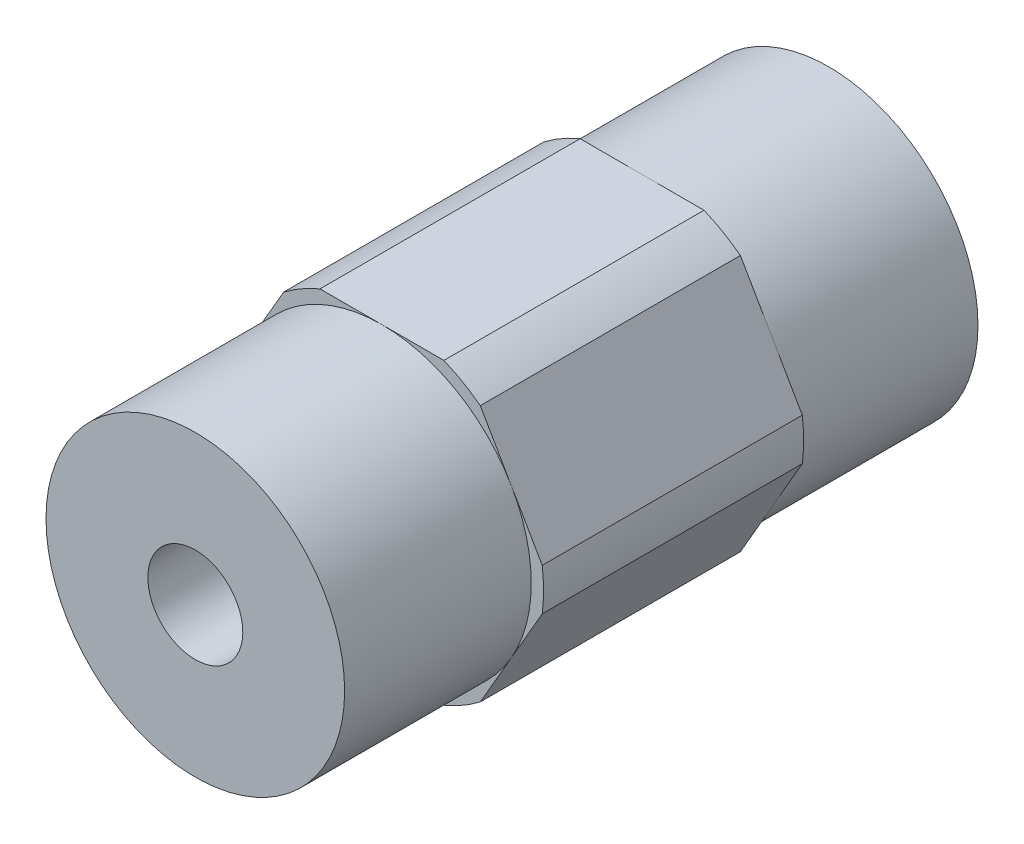
SolidWorks part; units mm, degrees
material "7075-T6 (SN)"
ref_plane "Front Plane" through (0, 0, 0) normal (0, 0, 1) x (1, 0, 0)
ref_plane "Top Plane" through (0, 0, 0) normal (0, 1, 0) x (1, 0, 0)
ref_plane "Right Plane" through (0, 0, 0) normal (1, 0, 0) x (0, 0, -1)
sketch "Sketch1" plane through (0, 0, 0) normal (0, 0, 1) x (1, 0, 0)
  line L1 (7.3323, 0) -> (3.6662, 6.35)
  line L2 (3.6662, 6.35) -> (-3.6662, 6.35)
  line L3 (-3.6662, 6.35) -> (-7.3323, 0)
  line L4 (-7.3323, 0) -> (-3.6662, -6.35)
  line L5 (-3.6662, -6.35) -> (3.6662, -6.35)
  line L6 (3.6662, -6.35) -> (7.3323, 0)
  circle A0 centre (0, 0) radius 6.35 construction
  circle A1 centre (0, 0) radius 2.0193
  circle A2 centre (0, 0) radius 6.875
  dimension "D1" = 12.7
  dimension "D2" = 4.0386
  dimension "D3" = 13.75
extrude "Boss-Extrude1" add sketch "Sketch1" along normal mid plane 26.9367 contours L1 A2 L2 L3 L4 L5 L6 A1 region at (6.6736, 0.4353, 0)
hole_wizard "#10-32 Tapped Hole1" positions "3DSketch1" profile "Sketch3" tap size "#10-32" standard "ANSI Inch"
sketch3d "3DSketch1"
  circle A0 centre (0, 0, -13.4684) radius 2.0193 construction
  circle A1 centre (0, 0, 13.4684) radius 2.0193 construction
  point P0 (0, 0, 13.4684)
  point P2 (0, 0, -13.4684)
  point P6 (0, 0, -11.449)
  point P9 (0, 0, 15.4877)
sketch "Sketch3" plane through (0, 0, 13.4684) normal (1, 0, 0) x (0, -1, 0)
  line L0 (0, 0) -> (0, 13.1513)
  line L1 (0, 13.1513) -> (2.0193, 11.938)
  line L2 (2.0193, 11.938) -> (2.0193, 0)
  line L5 (2.0193, 0) -> (0, 0)
  line L10 (0, 13.1513) -> (-2.0193, 11.938) construction
  line L11 (0, -6.35) -> (0, 107.95) construction
  dimension "Tap Drill Dia." = 4.0386
  dimension "Tap Drill Depth" = 11.938
  dimension "Drill Angle" = 118
cosmetic thread "Hole Thread1" parameters "D1"=9.652, "D2"=4.826
cosmetic thread "Hole Thread2" parameters "D1"=9.652, "D2"=4.826
sketch "Sketch4" plane through (0, 0, 13.4684) normal (0, 0, 1) x (1, 0, 0)
  circle A0 centre (0, 0) radius 6.35
  dimension "D1" = 12.7
extrude "Cut-Extrude-Thin1" cut sketch "Sketch4" against normal blind 7.9375 thin thin type one direction wall 2.54
mirror "Mirror1" about plane through (0, 0, 0) normal (0, 0, 1) of "Cut-Extrude-Thin1"
equation "\"D3@Sketch1\"=13.75mm"
